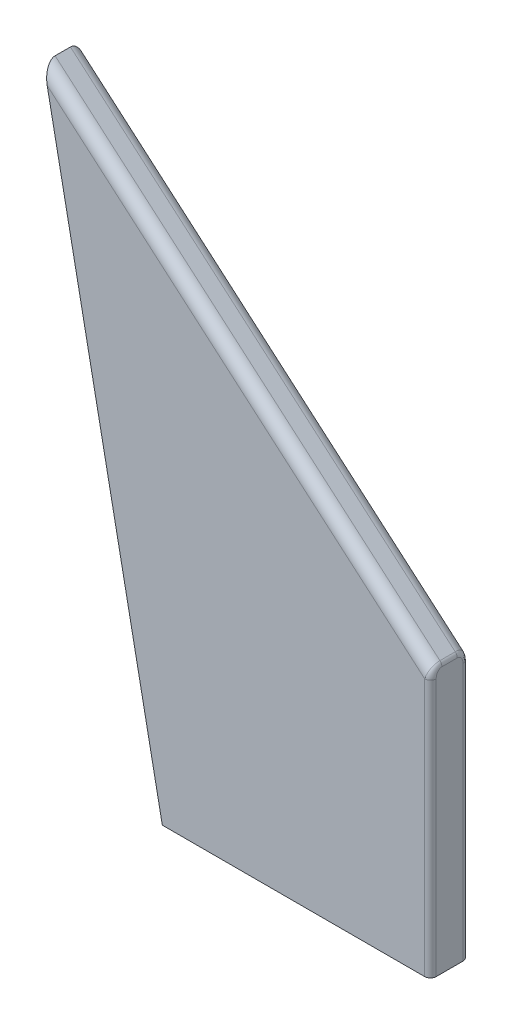
SolidWorks part; units mm, degrees
ref_plane "Front Plane" through (0, 0, 0) normal (0, 0, 1) x (1, 0, 0)
ref_plane "Top Plane" through (0, 0, 0) normal (0, 1, 0) x (1, 0, 0)
ref_plane "Right Plane" through (0, 0, 0) normal (1, 0, 0) x (0, 0, -1)
sketch "Sketch1" plane through (0, 0, 0) normal (0, 0, 1) x (1, 0, 0)
  line L0 (0, 0) -> (177.8, 0)
  line L1 (177.8, 0) -> (177.8, 177.8)
  line L2 (0, 0) -> (-78.7278, 398.7015)
  line L3 (-78.7278, 398.7015) -> (177.8, 177.8)
extrude "Boss-Extrude1" add sketch "Sketch1" along normal blind 25.4
fillet "Fillet1" radius 7.62 1 edges at (49.5361, 288.2508, 25.4)
fillet "Fillet2" radius 7.62 1 edges at (49.5361, 288.2508, 0)
fillet "Fillet3" radius 3.81 5 edges at (177.8, 83.8721, 0) (177.8, 174.8547, 2.2318) (177.8, 177.8, 12.7) (177.8, 174.8547, 23.1682) (177.8, 83.8721, 25.4)
